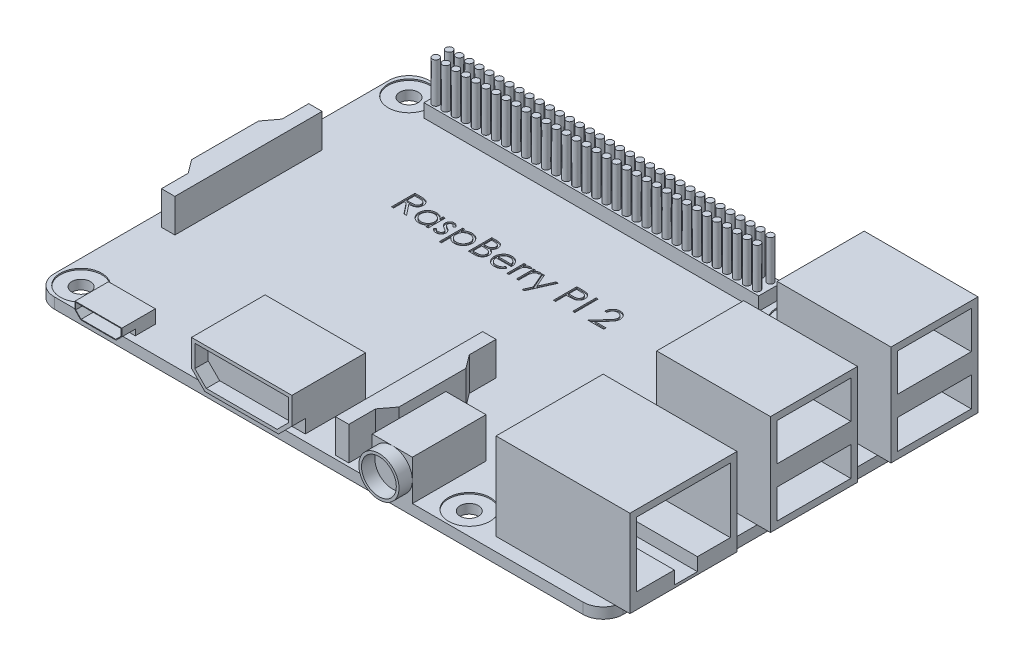
SolidWorks part; units mm, degrees
ref_plane "Plan de face" through (0, 0, 0) normal (0, 0, 1) x (1, 0, 0)
ref_plane "Plan de dessus" through (0, 0, 0) normal (0, 1, 0) x (1, 0, 0)
ref_plane "Plan de droite" through (0, 0, 0) normal (1, 0, 0) x (0, 0, -1)
sketch "Esquisse1" plane through (0, 0, 0) normal (0, 1, 0) x (1, 0, 0)
  line L0 (-46.4104, 0) -> (46.6241, 0) construction
  line L1 (39.5, 28) -> (-39.5, 28)
  line L2 (42.5, 25) -> (42.5, -25)
  line L3 (39.5, -28) -> (-39.5, -28)
  line L4 (-42.5, 25) -> (-42.5, -25)
  line L5 (42.5, 28) -> (-42.5, -28) construction
  line L6 (42.5, -28) -> (-42.5, 28) construction
  arc A0 (42.5, -25) -> (39.5, -28) centre (39.5, -25) cw
  arc A1 (39.5, 28) -> (42.5, 25) centre (39.5, 25) cw
  arc A2 (-39.5, -28) -> (-42.5, -25) centre (-39.5, -25) cw
  arc A3 (-39.5, 28) -> (-42.5, 25) centre (-39.5, 25) ccw
  circle A4 centre (-39, 24.5) radius 1.375
  circle A5 centre (19, 24.5) radius 1.375
  circle A6 centre (19, -24.5) radius 1.375
  circle A7 centre (-39, -24.5) radius 1.375
  point P0 (0, 0)
  dimension "D3" = 3
  dimension "D7" = 2.75
  dimension "D8" = 2.75
  dimension "D1" = 56
  dimension "D2" = 85
  dimension "D4" = 58
  dimension "D5" = 3.5
  dimension "D6" = 3.5
extrude "plaque" add sketch "Esquisse1" along normal blind 1.6
sketch "Esquisse2" plane through (0, 1.6, 0) normal (0, 1, 0) x (1, 0, 0)
  line L0 (27.5, 28) -> (27.5, -28) construction
  line L1 (39.5, 28) -> (-39.5, 28) construction
  line L2 (-39.5, -28) -> (39.5, -28) construction
  line L3 (42.5, -25) -> (42.5, 25) construction
  line L5 (27.5, 26) -> (44.5, 26)
  line L6 (27.5, 26) -> (27.5, 13)
  line L7 (27.5, 13) -> (44.5, 13)
  line L8 (44.5, 26) -> (44.5, 13)
  line L9 (27.5, 8) -> (44.5, 8)
  line L10 (27.5, 8) -> (27.5, -5)
  line L11 (27.5, -5) -> (44.5, -5)
  line L12 (44.5, 8) -> (44.5, -5)
  point P6 (27.5, 26)
  point P7 (27.5, 13)
  point P8 (27.5, 8)
  point P9 (27.5, -5)
  dimension "D1" = 2
  dimension "D2" = 13
  dimension "D3" = 15
  dimension "D4" = 5
  dimension "D5" = 13
  dimension "D6" = 17
  dimension "D7" = 17
extrude "USB" add sketch "Esquisse2" along normal blind 15
sketch "Esquisse3" plane through (0, 1.6, 0) normal (0, 1, 0) x (1, 0, 0)
  line L0 (24.5, -28) -> (24.5, 28) construction
  line L1 (-39.5, -28) -> (39.5, -28) construction
  line L2 (39.5, 28) -> (-39.5, 28) construction
  line L3 (42.5, -25) -> (42.5, -5) construction
  line L5 (24.5, -10) -> (44.5, -10)
  line L6 (24.5, -10) -> (24.5, -26)
  line L7 (24.5, -26) -> (44.5, -26)
  line L8 (44.5, -10) -> (44.5, -26)
  point P6 (24.5, -26)
  point P7 (24.5, -10)
  dimension "D1" = 2
  dimension "D2" = 16
  dimension "D3" = 18
  dimension "D4" = 20
extrude "RJ45" add sketch "Esquisse3" along normal blind 13
sketch "Esquisse4" plane through (0, 1.6, 0) normal (0, 1, 0) x (1, 0, 0)
  line L0 (-39, 24.5) -> (19, 24.5) construction
  line L2 (15, 26.266) -> (-35, 26.266)
  line L3 (15, 26.266) -> (15, 22.734)
  line L4 (15, 22.734) -> (-35, 22.734)
  line L5 (-35, 26.266) -> (-35, 22.734)
  line L6 (15, 26.266) -> (-35, 22.734) construction
  line L7 (15, 22.734) -> (-35, 26.266) construction
  point P4 (-10, 24.5)
  point P5 (-10, 24.5)
  dimension "D1" = 29
  dimension "D2" = 50
extrude "GPIO_Base" add sketch "Esquisse4" along normal blind 2
sketch "Esquisse5" plane through (0, 3.6, 0) normal (0, 1, 0) x (1, 0, 0)
  line L0 (-35, 24.5) -> (15, 24.5) construction
  line L1 (-35, 26.266) -> (-35, 22.734) construction
  line L2 (15, 22.734) -> (15, 26.266) construction
  line L3 (-35, 26.266) -> (-35, 22.734) construction
  circle A0 centre (-34, 25.5) radius 0.5
  circle A1 centre (-32.5, 25.5) radius 0.5
  circle A2 centre (-31, 25.5) radius 0.5
  circle A3 centre (-29.5, 25.5) radius 0.5
  circle A4 centre (-28, 25.5) radius 0.5
  circle A5 centre (-26.5, 25.5) radius 0.5
  circle A6 centre (-25, 25.5) radius 0.5
  circle A7 centre (-23.5, 25.5) radius 0.5
  circle A8 centre (-22, 25.5) radius 0.5
  circle A9 centre (-20.5, 25.5) radius 0.5
  circle A10 centre (-19, 25.5) radius 0.5
  circle A11 centre (-17.5, 25.5) radius 0.5
  circle A12 centre (-16, 25.5) radius 0.5
  circle A13 centre (-14.5, 25.5) radius 0.5
  circle A14 centre (-13, 25.5) radius 0.5
  circle A15 centre (-11.5, 25.5) radius 0.5
  circle A16 centre (-10, 25.5) radius 0.5
  circle A17 centre (-8.5, 25.5) radius 0.5
  circle A18 centre (-7, 25.5) radius 0.5
  circle A19 centre (-5.5, 25.5) radius 0.5
  circle A20 centre (-4, 25.5) radius 0.5
  circle A21 centre (-2.5, 25.5) radius 0.5
  circle A22 centre (-1, 25.5) radius 0.5
  circle A23 centre (0.5, 25.5) radius 0.5
  circle A24 centre (2, 25.5) radius 0.5
  circle A25 centre (3.5, 25.5) radius 0.5
  circle A26 centre (5, 25.5) radius 0.5
  circle A27 centre (6.5, 25.5) radius 0.5
  circle A28 centre (8, 25.5) radius 0.5
  circle A29 centre (9.5, 25.5) radius 0.5
  circle A30 centre (11, 25.5) radius 0.5
  circle A31 centre (12.5, 25.5) radius 0.5
  circle A32 centre (14, 25.5) radius 0.5
  circle A33 centre (-32.5, 23.5) radius 0.5
  circle A34 centre (-31, 23.5) radius 0.5
  circle A35 centre (-29.5, 23.5) radius 0.5
  circle A36 centre (-28, 23.5) radius 0.5
  circle A37 centre (-26.5, 23.5) radius 0.5
  circle A38 centre (-25, 23.5) radius 0.5
  circle A39 centre (-23.5, 23.5) radius 0.5
  circle A40 centre (-22, 23.5) radius 0.5
  circle A41 centre (-20.5, 23.5) radius 0.5
  circle A42 centre (-19, 23.5) radius 0.5
  circle A43 centre (-17.5, 23.5) radius 0.5
  circle A44 centre (-16, 23.5) radius 0.5
  circle A45 centre (-14.5, 23.5) radius 0.5
  circle A46 centre (-13, 23.5) radius 0.5
  circle A47 centre (-11.5, 23.5) radius 0.5
  circle A48 centre (-10, 23.5) radius 0.5
  circle A49 centre (-8.5, 23.5) radius 0.5
  circle A50 centre (-7, 23.5) radius 0.5
  circle A51 centre (-5.5, 23.5) radius 0.5
  circle A52 centre (-4, 23.5) radius 0.5
  circle A53 centre (-2.5, 23.5) radius 0.5
  circle A54 centre (-1, 23.5) radius 0.5
  circle A55 centre (0.5, 23.5) radius 0.5
  circle A56 centre (2, 23.5) radius 0.5
  circle A57 centre (3.5, 23.5) radius 0.5
  circle A58 centre (5, 23.5) radius 0.5
  circle A59 centre (6.5, 23.5) radius 0.5
  circle A60 centre (8, 23.5) radius 0.5
  circle A61 centre (9.5, 23.5) radius 0.5
  circle A62 centre (11, 23.5) radius 0.5
  circle A63 centre (12.5, 23.5) radius 0.5
  circle A64 centre (14, 23.5) radius 0.5
  circle A65 centre (-34, 23.5) radius 0.5
  dimension "D1" = 1
  dimension "D2" = 1
  dimension "D3" = 1
  dimension "D4" = 33
  dimension "D5" = 2
extrude "GPIO_Pins" add sketch "Esquisse5" along normal blind 6
sketch "Esquisse6" plane through (0, 1.6, 0) normal (0, 1, 0) x (1, 0, 0)
  line L0 (-42.5, -18) -> (19.4127, -18) construction
  line L1 (-42.5, 25) -> (-42.5, -25) construction
  line L2 (-39.5, -28) -> (39.5, -28) construction
  line L3 (-3, -18) -> (-18, -18)
  line L4 (-3, -18) -> (-3, -29)
  line L5 (-3, -29) -> (-18, -29)
  line L6 (-18, -18) -> (-18, -29)
  point P4 (-10.5, -18)
  dimension "D1" = 32
  dimension "D2" = 15
  dimension "D3" = 11
  dimension "D4" = 10
extrude "HDMI" add sketch "Esquisse6" along normal blind 6
ref_plane "Plan - USB - RJ45" through (44.5, 0, 0) normal (1, 0, 0) x (0, 0, -1)
sketch "Esquisse9" plane through (44.5, 0, 0) normal (1, 0, 0) x (0, 0, -1)
  line L1 (-4, 2.6) -> (7, 2.6)
  line L2 (-5, 16.6) -> (-5, 1.6) construction
  line L3 (-4, 7) -> (7, 7)
  line L4 (-4, 15.6) -> (-4, 10)
  line L6 (-5, 1.6) -> (8, 1.6) construction
  line L7 (-4, 10) -> (7, 10)
  line L8 (-4, 7) -> (-4, 2.6)
  line L9 (-4, 15.6) -> (7, 15.6)
  line L10 (7, 15.6) -> (7, 10)
  line L11 (-5, 16.6) -> (8, 16.6) construction
  line L12 (8, 16.6) -> (13, 1.6) construction
  line L13 (13, 1.6) -> (8, 1.6) construction
  line L14 (8, 1.6) -> (13, 16.6) construction
  line L15 (10.5, 9.1) -> (10.5, 20.2885) construction
  line L16 (14, 7) -> (14, 2.6)
  line L17 (25, 2.6) -> (14, 2.6)
  line L18 (25, 7) -> (25, 2.6)
  line L19 (25, 7) -> (14, 7)
  line L20 (25, 15.6) -> (25, 10)
  line L21 (25, 15.6) -> (14, 15.6)
  line L22 (14, 15.6) -> (14, 10)
  line L23 (25, 10) -> (14, 10)
  line L24 (-26, 14.6) -> (-26, 1.6) construction
  line L25 (-25, 13.6) -> (-11, 13.6)
  line L26 (-25, 13.6) -> (-25, 3.94)
  line L27 (-25, 3.94) -> (-19.3658, 3.94)
  line L28 (-11, 13.6) -> (-11, 3.94)
  line L29 (-26, 14.6) -> (-10, 14.6) construction
  line L30 (-10, 14.6) -> (-10, 1.6) construction
  line L31 (-19.3658, 3.94) -> (-19.3658, 2)
  line L32 (-19.3658, 2) -> (-15.9166, 2)
  line L33 (-15.9166, 2) -> (-15.9166, 3.94)
  line L34 (-15.9166, 3.94) -> (-11, 3.94)
  line L35 (7, 7) -> (7, 2.6)
  line L36 (8, 16.6) -> (8, 1.6) construction
  dimension "D1" = 1
  dimension "D2" = 1
  dimension "D3" = 1
  dimension "D4" = 1
  dimension "D5" = 1
  dimension "D6" = 1
  dimension "D7" = 1
extrude "USB - RJ45 - VIDE" cut sketch "Esquisse9" against normal blind 10
sketch "Esquisse10" plane through (0, 0, 29) normal (0, 0, 1) x (1, 0, 0)
  line L0 (-18, 3.6) -> (-16, 1.6)
  line L1 (-18, 7.6) -> (-18, 1.6) construction
  line L2 (-18, 1.6) -> (-3, 1.6) construction
  line L3 (-16, 1.6) -> (-18, 1.6)
  line L4 (-18, 1.6) -> (-18, 3.6)
  line L5 (-10.5, 7.6) -> (-10.5, 0) construction
  line L6 (-18, 7.6) -> (-3, 7.6) construction
  line L7 (-18, 3.6) -> (-18, 1.6)
  line L8 (-5, 1.6) -> (-3, 1.6)
  line L9 (-3, 1.6) -> (-3, 3.6)
  line L10 (-3, 3.6) -> (-5, 1.6)
  line L11 (-15.7929, 2.1) -> (-5.2071, 2.1)
  line L12 (-5.2071, 2.1) -> (-3.5, 3.8071)
  line L13 (-3.5, 3.8071) -> (-3.5, 7.1)
  line L14 (-3.5, 7.1) -> (-17.5, 7.1)
  line L15 (-17.5, 7.1) -> (-17.5, 3.8071)
  line L16 (-17.5, 3.8071) -> (-15.7929, 2.1)
  line L17 (-3, 7.6) -> (-3, 1.6) construction
  line M1 (-18, 1.6) -> (-3, 1.6)
  line M2 (-3, 1.6) -> (-3, 7.6)
  line M4 (-18, 7.6) -> (-18, 1.6)
  dimension "D1" = 2
  dimension "D2" = 2
  dimension "D3" = 0.5
  dimension "D4" = 0.5
  dimension "D5" = 0.5
  dimension "D6" = 0.5
  dimension "D7" = 0.5
  dimension "D8" = 0.5
extrude "HDMI - VIDE" cut sketch "Esquisse10" against normal blind 2 contours L0 M4 M1 | L10 M2 M1 | L14 L5 L11 L12 L13 | L5 L14 L15 L16 L11 region at (-13.8727, 4.6839, 29) region at (-7.1273, 4.6839, 29) region at (-3.6667, 2.2667, 29) region at (-17.3333, 2.2667, 29)
sketch "Esquisse11" plane through (0, 1.6, 0) normal (0, 1, 0) x (1, 0, 0)
  text T0 "RaspBerry PI 2 "
extrude "RaspBerry Pi 2 " cut sketch "Esquisse11" against normal blind 0.2
sketch "Esquisse12" plane through (0, 1.6, 0) normal (0, 1, 0) x (1, 0, 0)
  line L0 (-39.5, -28) -> (-16, -28) construction
  line L1 (-42.5, 25) -> (-42.5, -25) construction
  line L2 (-36.513, 0) -> (-38.9859, 0) construction
  line L3 (-5, -28) -> (39.5, -28) construction
  line L4 (-38.9859, -10.884) -> (-38.9859, 9.7054) construction
  line L5 (-38.4859, 11) -> (-38.4859, -11)
  line L6 (-38.4859, -11) -> (-40.4859, -11)
  line L7 (-40.4859, -11) -> (-40.4859, -7)
  line L8 (-41.9859, 5) -> (-41.9859, -5)
  line L9 (-40.4859, -7) -> (-41.9859, -5)
  line L10 (-38.4859, 11) -> (-40.4859, 11)
  line L11 (-40.4859, 11) -> (-40.4859, 7)
  line L12 (-40.4859, 7) -> (-41.9859, 5)
  line L13 (2.5, -6.1303) -> (2.5, -24.8834) construction
  line L14 (0, -16.5) -> (5.9658, -16.5) construction
  line L16 (3, -27.5) -> (2, -27.5)
  line L20 (3, -5.5) -> (2, -5.5)
  line L23 (2, -27.5) -> (4, -27.5)
  line L24 (4, -27.5) -> (4, -23.5)
  line L25 (4, -23.5) -> (5.5, -21.5)
  line L26 (5.5, -21.5) -> (5.5, -11.5)
  line L27 (4, -9.5) -> (5.5, -11.5)
  line L28 (2, -5.5) -> (2, -27.5)
  line L29 (2, -5.5) -> (4, -5.5)
  line L30 (4, -5.5) -> (4, -9.5)
  point P0 (-38.9859, 0)
  point P3 (2.5, -16.5)
  point P14 (-38.4859, 0)
  point P22 (-41.9859, 0)
  point P28 (3, -16.5)
  point P36 (-0.5, -16.5)
  dimension "D1" = 28
  dimension "D2" = 45
  dimension "D3" = 11.5
  dimension "D4" = 0.5
  dimension "D5" = 22
  dimension "D6" = 2
  dimension "D7" = 4
  dimension "D8" = 3.5
  dimension "D9" = 2.5
  dimension "D10" = 22
extrude "CONNECTIQUES" add sketch "Esquisse12" along normal blind 5 contours L11 L12 L8 L9 L7 L6 L5 L10 | L30 L29 L20 L28 L16 L23 L24 L25 L26 L27 region at (-39.9819, 1.6, 0) region at (3.496, 1.6, 16.5)
sketch "Esquisse13" plane through (0, 0, 0) normal (0, -1, 0) x (1, 0, 0)
  line L0 (-42.5, -25) -> (-42.5, 25) construction
  line L1 (-42.5, 3.8116) -> (-28.5, 3.8116)
  line L2 (-42.5, -7.1884) -> (-42.5, -8.1884)
  line L3 (-42.5, -8.1884) -> (-28.5, -8.1884)
  line L4 (-28.5, 3.8116) -> (-28.5, -8.1884)
  line L5 (-42.5, 3.8116) -> (-28.5, -8.1884) construction
  line L6 (-42.5, -8.1884) -> (-28.5, 3.8116) construction
  line L7 (-42.5, 3.8116) -> (-44.5, 3.8116)
  line L8 (-44.5, 3.8116) -> (-44.5, -7.1884)
  line L9 (-44.5, -7.1884) -> (-42.5, -7.1884)
  point P0 (-35.5, -2.1884)
  point P1 (-35.5, -2.1884)
  dimension "D1" = 12
  dimension "D2" = 14
  dimension "D3" = 11
  dimension "D4" = 2
extrude "MICRO SD" add sketch "Esquisse13" along normal blind 1
sketch "Esquisse14" plane through (0, 1.6, 0) normal (0, 1, 0) x (1, 0, 0)
  line L0 (-42.5, 25) -> (-42.5, -25) construction
  line L1 (-5, -28) -> (39.5, -28) construction
  line L2 (8, -28) -> (14, -28)
  line L3 (8, -28) -> (8, -17)
  line L4 (8, -17) -> (14, -17)
  line L5 (14, -28) -> (14, -17)
  line L6 (8, -28) -> (14, -17) construction
  line L7 (8, -17) -> (14, -28) construction
  point P0 (11, -22.5)
  point P3 (11, -22.5)
  dimension "D1" = 53.5
  dimension "D2" = 11
  dimension "D3" = 6
extrude "JACK BASE" add sketch "Esquisse14" along normal blind 6
sketch "Esquisse15" plane through (0, 0, 28) normal (0, 0, 1) x (1, 0, 0)
  line L0 (8, 1.6) -> (14, 1.6) construction
  line L1 (8, 7.6) -> (14, 1.6) construction
  line L2 (8, 7.6) -> (14, 7.6) construction
  circle A0 centre (11, 4.6) radius 3
  circle A1 centre (11, 4.6) radius 2.6
  dimension "D1" = 0.4
extrude "JACK ROND" add sketch "Esquisse15" along normal blind 2
sketch "Esquisse16" plane through (0, 1.6, 0) normal (0, 1, 0) x (1, 0, 0)
  circle A0 centre (-39, -24.5) radius 3.1
  circle A1 centre (-39, 24.5) radius 3.1
  circle A2 centre (19, 24.5) radius 3.1
  circle A3 centre (19, -24.5) radius 3.1
  dimension "D1" = 6.2
  dimension "D2" = 6.2
  dimension "D3" = 6.2
  dimension "D4" = 6.2
extrude "TROU FIXATION - VIDE" cut sketch "Esquisse16" against normal blind 0.2
sketch "Esquisse17" plane through (0, 1.6, 0) normal (0, 1, 0) x (1, 0, 0)
  line L0 (-42.5, 25) -> (-42.5, -25) construction
  line L1 (-35.4, -24) -> (-28.4, -24)
  line L2 (-35.4, -24) -> (-35.4, -29)
  line L3 (-39.5, -28) -> (-16, -28) construction
  line L4 (-28.4, -24) -> (-28.4, -29)
  line L5 (-28.4, -29) -> (-35.4, -29)
  point P0 (-31.9, -24)
  dimension "D1" = 10.6
  dimension "D2" = 7
  dimension "D3" = 5
  dimension "D4" = 4
extrude "MICRO USB BASE" add sketch "Esquisse17" along normal blind 2
sketch "Esquisse18" plane through (0, 0, 29) normal (0, 0, 1) x (1, 0, 0)
  line L0 (-35.4, 2.4712) -> (-34.5288, 1.6)
  line L1 (-35.4, 3.6) -> (-35.4, 1.6) construction
  line L2 (-35.4, 1.6) -> (-28.4, 1.6) construction
  line L3 (-34.5288, 1.6) -> (-35.4, 1.6)
  line L4 (-35.4, 1.6) -> (-35.4, 2.4712)
  line L5 (-35.4, 3.6) -> (-28.4, 1.6) construction
  line L6 (-35, 1.6) -> (15, 1.6) construction
  line L7 (-35.4, 1.6) -> (-28.4, 1.6) construction
  line L8 (-31.9, 2.6) -> (-31.9, 4.471) construction
  line L9 (-35.4, 2.4712) -> (-35.4, 1.6)
  line L10 (-35.4, 1.6) -> (-35.373, 1.5876)
  line L11 (-29.2712, 1.6) -> (-28.4, 1.6)
  line L12 (-28.4, 1.6) -> (-28.4, 2.4712)
  line L13 (-28.4, 2.4712) -> (-29.2712, 1.6)
  line L14 (-35.3, 3.5) -> (-35.3, 2.5126)
  line L15 (-35.3, 2.5126) -> (-34.4874, 1.7)
  line L16 (-34.4874, 1.7) -> (-29.3126, 1.7)
  line L17 (-35.3, 3.5) -> (-28.5, 3.5)
  line L18 (-35.4, 3.6) -> (-28.4, 3.6) construction
  line L19 (-28.5, 2.5126) -> (-29.3126, 1.7)
  line L20 (-28.5, 3.5) -> (-28.5, 2.5126)
  point P28 (-31.9, 1.7)
  point P30 (-31.9, 3.5)
  line M1 (-35.4, 1.6) -> (-28.4, 1.6)
  line M2 (-28.4, 1.6) -> (-28.4, 3.6)
  line M4 (-35.4, 3.6) -> (-35.4, 1.6)
  dimension "D1" = 0.1
  dimension "D2" = 0.1
  dimension "D3" = 0.1
  dimension "D4" = 0.1
extrude "MICRO USB - VIDE" cut sketch "Esquisse18" against normal blind 2 contours L20 L17 L14 L15 L16 L19 | L0 M4 M1 | L13 M2 M1 region at (-28.6904, 1.8904, 29) region at (-35.1096, 1.8904, 29) region at (-31.9, 2.6359, 29)
